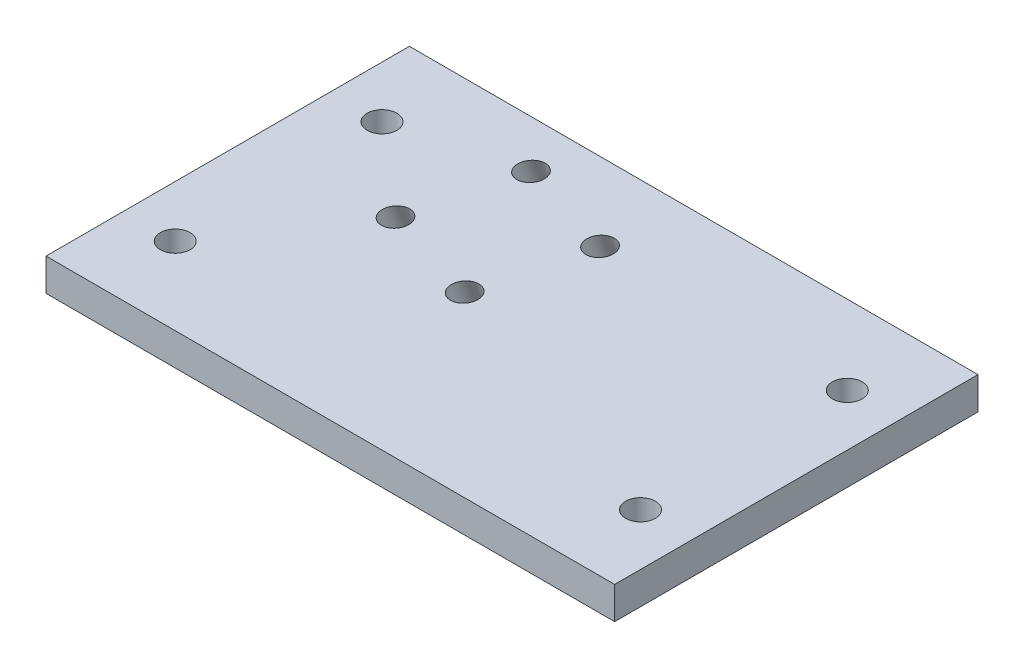
SolidWorks part; units mm, degrees
ref_plane "Front" through (0, 0, 0) normal (0, 0, 1) x (1, 0, 0)
ref_plane "Top" through (0, 0, 0) normal (0, 1, 0) x (1, 0, 0)
ref_plane "Right" through (0, 0, 0) normal (1, 0, 0) x (0, 0, -1)
sketch "Sketch1" plane through (0, 0, 0) normal (0, 1, 0) x (1, 0, 0)
  line L1 (0, 0) -> (90, 0)
  line L2 (0, 0) -> (0, 56.23)
  line L3 (0, 56.23) -> (90, 56.23)
  line L4 (90, 0) -> (90, 56.23)
  dimension "D1" = 90
  dimension "D2" = 56.23
extrude "Boss-Extrude1" add sketch "Sketch1" along normal blind 5
sketch "Sketch2" plane through (0, 5, 0) normal (0, 1, 0) x (1, 0, 0)
  circle A0 centre (82, 12) radius 2.3
  circle A1 centre (10, 12) radius 2.3
extrude "Cut-Extrude1" cut sketch "Sketch2" against normal blind 15
sketch "Sketch4" plane through (0, 5, 0) normal (0, 1, 0) x (1, 0, 0)
  circle A0 centre (39.2121, 27.5705) radius 2.2
  circle A1 centre (23.8176, 32.2728) radius 2.2
  circle A2 centre (43.572, 44.174) radius 2.2
  circle A3 centre (28.1775, 48.8763) radius 2.2
ref_plane "Plane1" through (0, 4.2983, 1.7366) normal (0, 0.9272, 0.3746) x (1, 0, 0)
sketch "Sketch6" plane through (0, 4.2983, 1.7366) normal (0, 0.9272, 0.3746) x (1, 0, 0)
  circle A0 centre (28.1775, 47.1904) radius 2.0398
  circle A1 centre (23.8176, 31.7959) radius 2.0398
  circle A2 centre (39.2121, 27.436) radius 2.0398
  circle A3 centre (43.572, 42.8305) radius 2.0398
extrude "Cut-Extrude2" cut sketch "Sketch6" against normal blind 45
sketch "Sketch7" plane through (0, 5, 0) normal (0, 1, 0) x (1, 0, 0)
  circle A0 centre (82, 44) radius 2.3
  circle A1 centre (10, 44) radius 2.3
extrude "Cut-Extrude3" cut sketch "Sketch7" against normal blind 45
sketch "Sketch8" plane through (0, 0, 0) normal (-1, 0, 0) x (0, 0, 1)
  circle A0 centre (-29.8532, 2.0033) radius 1.2661
sketch "Sketch9" plane through (0, 0, 0) normal (-1, 0, 0) x (0, 0, 1)
  line L1 (-56.23, 0) -> (4.9539, 0)
  line L2 (-56.23, 0) -> (-56.23, 5.0439)
  line L3 (-56.23, 5.0439) -> (4.9539, 5.0439)
  line L4 (4.9539, 0) -> (4.9539, 5.0439)
extrude "Cut-Extrude4" cut sketch "Sketch9" against normal blind 2
